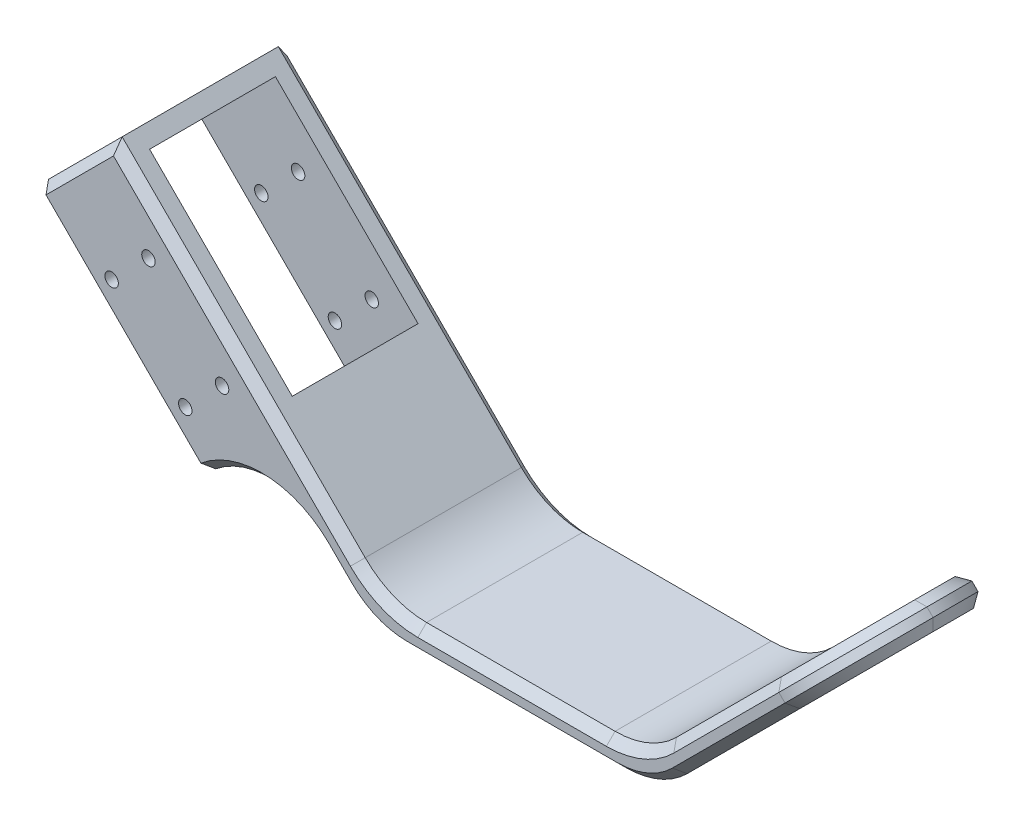
SolidWorks part; units mm, degrees
ref_plane "Front Plane" through (0, 0, 0) normal (0, 0, 1) x (1, 0, 0)
ref_plane "Top Plane" through (0, 0, 0) normal (0, 1, 0) x (1, 0, 0)
ref_plane "Right Plane" through (0, 0, 0) normal (1, 0, 0) x (0, 0, -1)
sketch "Sketch1" plane through (0, 0, 0) normal (0, 0, 1) x (1, 0, 0)
  line L0 (65, 0) -> (110.9619, 45.9619) construction
  line L1 (0, 0) -> (65, 0)
  line L2 (0, 0) -> (0, 6)
  line L3 (0, 6) -> (65, 6)
  line L4 (65, 0) -> (65, 6)
  line L5 (65, 0) -> (59, 6) construction
  line L6 (60.7574, 4.2426) -> (65, 0)
  line L7 (60.7574, 4.2426) -> (106.7193, 50.2046)
  line L8 (65, 0) -> (110.9619, 45.9619)
  line L9 (106.7193, 50.2046) -> (110.9619, 45.9619)
  line L10 (0, 0) -> (-63.6396, 63.6396) construction
  line L11 (0, 0) -> (6, 6) construction
  line L12 (4.2426, 4.2426) -> (0, 0)
  line L13 (4.2426, 4.2426) -> (-59.397, 67.8823)
  line L14 (0, 0) -> (-63.6396, 63.6396)
  line L15 (-59.397, 67.8823) -> (-63.6396, 63.6396)
  dimension "D1" = 65
  dimension "D2" = 6
  dimension "D3" = 45
  dimension "D4" = 6
  dimension "D5" = 65
  dimension "D6" = 90
  dimension "D7" = 6
  dimension "D8" = 45
  dimension "D9" = 90
  dimension "D10" = 90
extrude "Boss-Extrude1" add sketch "Sketch1" along normal blind 40 contours L13 L15 L14 L2 L3 | L12 L13 L3 L2 | L13 L12 L1 L6 L7 L3 | L7 L6 L4 L3 | L9 L7 L3 L4 L8 region at (32.5, 2.9415, 0) region at (-30.5855, 34.7997, 0) region at (1.5355, 3.7071, 0) region at (63.4645, 3.7071, 0) region at (86.75, 25.9529, 0)
sketch "Sketch2" plane through (28.2574, -28.2574, 0) normal (-0.7071, 0.7071, 0) x (0, 0, 1)
  line L0 (0, 110.9619) -> (40, 70.9619) construction
  line L1 (40, 48.4472) -> (40, 110.9619) construction
  line L2 (40, 110.9619) -> (0, 110.9619) construction
  circle A0 centre (20, 90.9619) radius 4
  circle A1 centre (20, 98.9619) radius 1.5
  circle A2 centre (28, 90.9619) radius 1.5
  circle A3 centre (20, 90.9619) radius 4
  circle A4 centre (20, 82.9619) radius 1.5
  circle A5 centre (20, 90.9619) radius 4
  circle A6 centre (12, 90.9619) radius 1.5
  circle A7 centre (20, 90.9619) radius 4
  point P11 (0, 0)
  point P21 (20, 90.9619)
  point P22 (0, 0)
  dimension "D1" = 3
  dimension "D2" = 8
  dimension "D4" = 45
  dimension "D5" = 0
  dimension "D3" = 4
extrude "Cut-Extrude1" cut sketch "Sketch2" against normal blind 40 contours A4 | A6 | A0 L0 | L0 A7 | A1 | A2 region at (93.426, 36.9113, 21.2004) region at (91.7283, 35.2136, 18.7996) region at (98.234, 41.7193, 20) region at (92.5772, 36.0624, 28) region at (86.9203, 30.4056, 20) region at (92.5772, 36.0624, 12)
sketch "Sketch3" plane through (0, 0, 0) normal (-0.7071, -0.7071, 0) x (0, 0, 1)
  line L0 (40, 0) -> (40, 90) construction
  line L1 (0, 90) -> (40, 90)
  line L2 (0, 90) -> (0, 35.5)
  line L3 (0, 35.5) -> (40, 35.5)
  line L4 (40, 90) -> (40, 35.5)
  line L5 (4, 86) -> (4, 39.5)
  line L6 (4, 39.5) -> (36, 39.5)
  line L7 (36, 86) -> (36, 39.5)
  line L8 (4, 86) -> (36, 86)
  line L9 (5.5, 86) -> (5.5, 39.5)
  line L10 (5.5, 86) -> (34.5, 86)
  line L11 (20, 86) -> (20, 39.5)
  line L12 (5.5, 39.5) -> (34.5, 39.5)
  line L13 (34.5, 86) -> (34.5, 39.5)
  line M13 (0, 90) -> (0, 0)
  line M15 (40, 0) -> (40, 90)
  line M16 (40, 90) -> (0, 90)
  dimension "D1" = 54.5
  dimension "D3" = 14.5
  dimension "D2" = 4
extrude "Boss-Extrude2" add sketch "Sketch3" along normal blind 18 contours L3 L5 L8 L10 L7 L6 M13 M15 M16 | L9 L8 L5 L6 | L8 L13 L6 L7 region at (-63.1616, 63.1616, 20) region at (-44.371, 44.371, 4.75) region at (-44.371, 44.371, 35.25)
sketch "Sketch4" plane through (0, 0, 0) normal (-0.7071, -0.7071, 0) x (0, 0, 1)
  line L4 (5.5, 86) -> (5.5, 39.5)
  line L5 (5.5, 39.5) -> (34.5, 39.5)
  line L6 (34.5, 39.5) -> (34.5, 86)
  line L7 (34.5, 86) -> (5.5, 86)
  line L8 (5.5, 86) -> (5.5, 39.5)
  line L9 (5.5, 39.5) -> (34.5, 39.5)
  line L10 (34.5, 39.5) -> (34.5, 86)
  line L11 (34.5, 86) -> (5.5, 86)
  dimension "D1" = 0
extrude "Cut-Extrude2" cut sketch "Sketch4" against normal blind 40
sketch "Sketch5" plane through (0, 0, 40) normal (0, 0, 1) x (1, 0, 0)
  circle A0 centre (-59.8212, 40.1637) radius 1.05 construction
  circle A1 centre (-42.8507, 23.1931) radius 1.05 construction
  circle A2 centre (-34.3654, 31.6784) radius 1.05 construction
  circle A3 centre (-51.336, 48.6489) radius 1.05 construction
  circle A4 centre (-59.8212, 40.1637) radius 1.05
  circle A5 centre (-42.8507, 23.1931) radius 1.05
  circle A6 centre (-34.3654, 31.6784) radius 1.05
  circle A7 centre (-51.336, 48.6489) radius 1.05
  circle A9 centre (-59.8212, 40.1637) radius 1.55
  circle A10 centre (-51.336, 48.6489) radius 1.55
  circle A11 centre (-51.336, 48.6489) radius 1.55
  circle A12 centre (-42.8507, 23.1931) radius 1.55
  circle A13 centre (-34.3654, 31.6784) radius 1.55
  dimension "D1" = 0.5
  dimension "D2" = 0.5
extrude "Cut-Extrude3" cut sketch "Sketch5" against normal through all both contours A11 A7 | A7 | A9 A4 | A4 | A13 A6 | A6 | A12 A5 | A5 region at (-59.8212, 40.1637, 40) region at (-42.8507, 23.1931, 40) region at (-34.3654, 31.6784, 40) region at (-51.336, 48.6489, 40) region at (-61.3274, 40.1637, 40) region at (-52.8421, 48.6489, 40) region at (-44.3568, 23.1931, 40) region at (-35.8715, 31.6784, 40)
fillet "Fillet1" radius 20 4 edges at (0, 0, 20) (2.4853, 6, 20) (62.5147, 6, 20) (65, 0, 20)
fillet "Fillet2" radius 20 1 edges at (-25.1023, 25.1023, 20)
fillet "Fillet3" radius 20 2 edges at (108.8406, 48.0833, 0) (108.8406, 48.0833, 40)
chamfer "Chamfer1" distance 2 angle 45 28 edges at (-67.8823, 59.397, 0) (-67.8823, 59.397, 40) (-24.1719, 16.8638, 0) (-8.4445, 8.4445, 0) (0.6306, 1.5224, 0) (32.5, 0, 0) (64.3694, 1.5224, 0) (83.8388, 18.8388, 0) (106.8198, 41.8198, 5.8579) (-24.1719, 16.8638, 40) (106.8198, 41.8198, 34.1421) (-8.4445, 8.4445, 40) (83.8388, 18.8388, 40) (0.6306, 1.5224, 40) (64.3694, 1.5224, 40) (32.5, 0, 40) (-31.3848, 39.8701, 0) (3.1159, 7.5224, 0) (32.5, 6, 0) (61.8841, 7.5224, 0) (80.4749, 23.9602, 0) (102.5772, 46.0624, 5.8579) (102.5772, 46.0624, 34.1421) (-31.3848, 39.8701, 40) (80.4749, 23.9602, 40) (3.1159, 7.5224, 40) (61.8841, 7.5224, 40) (32.5, 6, 40)
